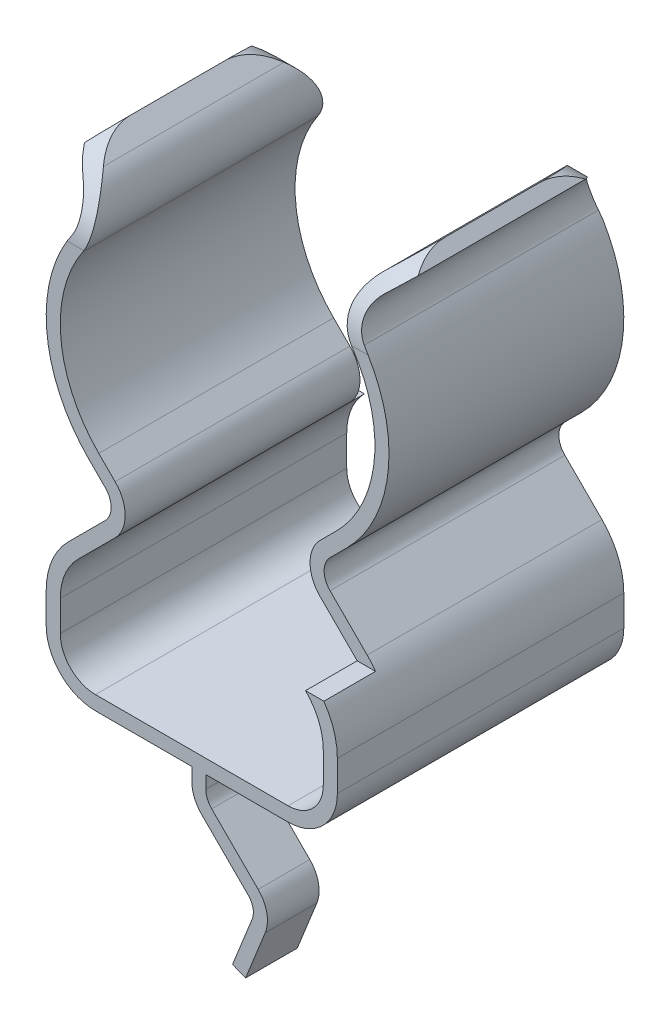
SolidWorks part; units mm, degrees
ref_plane "Plan de face" through (0, 0, 0) normal (0, 0, 1) x (1, 0, 0)
ref_plane "Plan de dessus" through (0, 0, 0) normal (0, 1, 0) x (1, 0, 0)
ref_plane "Plan de droite" through (0, 0, 0) normal (1, 0, 0) x (0, 0, -1)
sketch "Esquisse2" plane through (0, 0, 0) normal (0, 0, 1) x (1, 0, 0)
  line L0 (0, 0) -> (2.05, 0)
  line L1 (2.8, 0.75) -> (2.8, 1.4002)
  line L2 (2.4232, 2.3099) -> (1.6325, 3.1006)
  line L3 (1.6325, 4.1356) -> (1.9799, 4.483)
  line L4 (1.6325, 4.1356) -> (1.6325, 3.1006) construction
  line L5 (2.15, 3.6181) -> (1.6325, 3.6181) construction
  line L6 (0, 0) -> (0, 11.2116) construction
  line L7 (2.8, -3.5165) -> (2.8, 11.2116) construction
  line L8 (2.4583, 9.246) -> (2.8, 9.5636)
  line L9 (0.2119, -1.0822) -> (1.2017, -2.072)
  line L10 (0.8677, -3.5165) -> (1.2847, -2.4773)
  line L11 (0, 0) -> (0, -0.5706)
  arc A0 (2.05, 0) -> (2.8, 0.75) centre (2.05, 0.75) ccw
  arc A1 (2.8, 1.4002) -> (2.4232, 2.3099) centre (1.5134, 1.4002) ccw
  arc A2 (1.6325, 3.1006) -> (1.6325, 4.1356) centre (2.15, 3.6181) cw
  arc A3 (1.9799, 4.483) -> (2.3195, 8.0313) centre (0, 6.4629) ccw
  arc A4 (2.3195, 8.0313) -> (2.4583, 9.246) centre (3.098, 8.5576) cw
  arc A5 (0.2119, -1.0822) -> (0, -0.5706) centre (0.7234, -0.5706) cw
  arc A6 (1.2017, -2.072) -> (1.2847, -2.4773) centre (0.9362, -2.3375) cw
  dimension "D2" = 0.75
  dimension "D3" = 45
  dimension "D1" = 2.8
  dimension "D4" = 45
extrude "Extru.-Mince1" add sketch "Esquisse2" along normal mid plane 6.1 thin contours L10 A6 L9 A5 L11 L0 A0 L1 A1 L2 A2 L3 A3 A4 L8 thin type one direction wall 0.3
sketch "Esquisse3" plane through (0, 0, 0) normal (1, 0, 0) x (0, 0, -1)
  line L0 (-3.05, -3.6282) -> (3.05, -3.6282) construction
  line L1 (-1.95, -3.6282) -> (3.05, -3.6282)
  line L2 (-1.95, -3.6282) -> (-1.95, -0.3)
  line L3 (-1.95, -0.3) -> (3.05, -0.3)
  line L4 (3.05, -3.6282) -> (3.05, -0.3)
  line L5 (-3.05, -0.3) -> (3.05, -0.3) construction
  line L6 (3.05, 9.5636) -> (1.55, 9.5636)
  line L7 (-3.05, 9.5636) -> (3.05, 9.5636) construction
  line L8 (3.05, 9.5636) -> (3.05, 8.0636)
  line L9 (3.05, 8.0313) -> (3.05, 9.246) construction
  line L10 (3.05, 8.0636) -> (-1.95, 8.0636) construction
  line L12 (1.55, 9.5636) -> (1.55, 8.0636) construction
  line L13 (-0.45, 9.5636) -> (-3.05, 9.5636)
  line L14 (-3.05, 9.246) -> (-3.05, 9.5636) construction
  line L15 (-0.45, 9.5636) -> (-0.45, 8.0636) construction
  line L17 (-1.95, 8.0636) -> (-1.95, 2.3099)
  line L18 (-1.95, 2.3099) -> (-3.05, 2.3099)
  line L19 (-3.05, 2.3099) -> (-3.05, 1.4002) construction
  line L20 (-3.05, 2.3099) -> (-3.05, 9.5636)
  line L21 (-1.95, 2.3099) -> (-1.95, -0.3) construction
  arc A0 (1.55, 9.5636) -> (3.05, 8.0636) centre (1.55, 8.0636) cw
  arc A1 (-1.95, 8.0636) -> (-0.45, 9.5636) centre (-0.45, 8.0636) cw
  dimension "D1" = 1.1
  dimension "D2" = 1.5
extrude "Enlèv. mat.-Extru.1" cut sketch "Esquisse3" along normal blind 10
ref_axis "Axe1" through (0, -4.2878, 0) along (0, 1, 0)
pattern_circular "Répétition circulaire1" count 2 over 360 about axis through (0, -4.2878, 0) along (0, 1, 0) of "Extru.-Mince1", "Enlèv. mat.-Extru.1"
